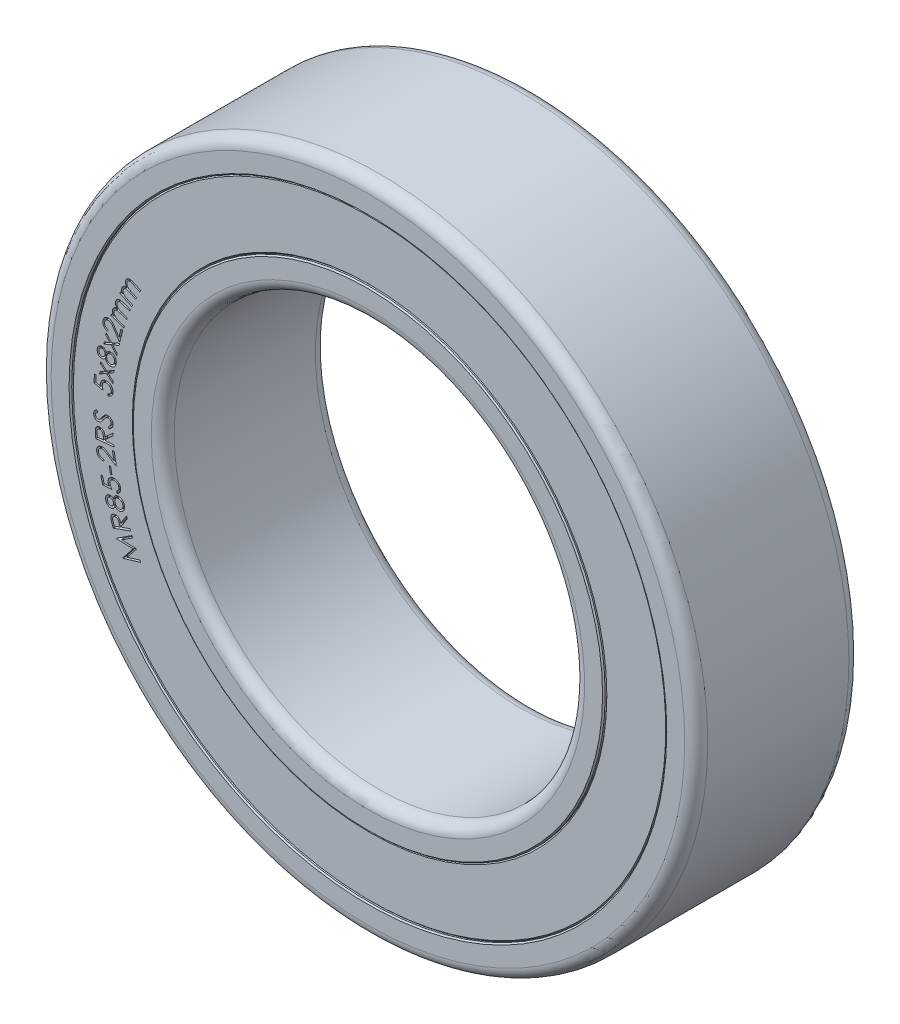
SolidWorks part; units mm, degrees
material "AISI 316 Annealed Stainless Steel Bar (SS)"
ref_plane "Front" through (0, 0, 0) normal (0, 0, 1) x (1, 0, 0)
ref_plane "Top" through (0, 0, 0) normal (0, 1, 0) x (1, 0, 0)
ref_plane "Right" through (0, 0, 0) normal (1, 0, 0) x (0, 0, -1)
sketch "LAYOUT R" plane through (0, 0, 0) normal (1, 0, 0) x (0, 0, -1)
  line L0 (-1, 2.5) -> (1, 2.5)
  line L1 (1, -4) -> (-1, -4) construction
  line L2 (1, -4) -> (1, 4) construction
  line L3 (1, 4) -> (-1, 4)
  line L4 (-1, -4) -> (-1, 4) construction
  line L5 (1, -4) -> (-1, 4) construction
  line L6 (1, 4) -> (-1, -4) construction
  line L7 (-1, 2.875) -> (1, 2.875)
  line L8 (-1, 3.625) -> (1, 3.625)
  line L11 (-17.5, 0) -> (17.5, 0) construction
  line L12 (-1, 4) -> (-1, 3.625)
  line L13 (1, 4) -> (1, 3.625)
  line L14 (-1, 3.625) -> (-1, 2.875)
  line L15 (1, 3.625) -> (1, 2.875)
  line L16 (-1, 2.875) -> (-1, 2.5)
  line L17 (1, 2.875) -> (1, 2.5)
  line L18 (-0.98, 3.625) -> (-0.98, 2.875)
  line L19 (0.98, 3.625) -> (0.98, 2.875)
  point P0 (0, 0)
  point P15 (0, 0)
  dimension "D1" = 2
  dimension "D2" = 8
  dimension "D3" = 2.5
  dimension "D6" = 0.02
  dimension "D7" = 0.02
  dimension "D4" = 2.875
  dimension "D5" = 3.625
sketch "Sketch R, INNER BODY" plane through (0, 0, 0) normal (1, 0, 0) x (0, 0, -1)
  line L0 (-1, 2.5) -> (1, 2.5) construction
  line L2 (-1, 2.875) -> (1, 2.875) construction
  line L4 (-1, 2.5) -> (1, 2.5)
  line L6 (-1, 2.875) -> (1, 2.875)
  line L8 (1, 2.875) -> (1, 2.5) construction
  line L9 (-1, 2.875) -> (-1, 2.5) construction
  line L10 (1, 2.875) -> (1, 2.5)
  line L11 (-1, 2.875) -> (-1, 2.5)
  line L12 (-17.5, 0) -> (17.5, 0) construction
  line L13 (-17.5, 0) -> (17.5, 0) construction
sketch "Sketch R, OUTER BODY" plane through (0, 0, 0) normal (1, 0, 0) x (0, 0, -1)
  line L2 (-1, 3.625) -> (1, 3.625) construction
  line L3 (1, 4) -> (-1, 4) construction
  line L6 (-1, 3.625) -> (1, 3.625)
  line L7 (1, 4) -> (-1, 4)
  line L8 (-17.5, 0) -> (17.5, 0) construction
  line L9 (-17.5, 0) -> (17.5, 0) construction
  line L10 (1, 4) -> (1, 3.625) construction
  line L11 (-1, 4) -> (-1, 3.625) construction
  line L12 (1, 4) -> (1, 3.625)
  line L13 (-1, 4) -> (-1, 3.625)
sketch "Sketch R, SEAL FACES" plane through (0, 0, 0) normal (1, 0, 0) x (0, 0, -1)
  line L0 (-17.5, 0) -> (17.5, 0) construction
  line L1 (-17.5, 0) -> (17.5, 0) construction
  line L3 (-1, 2.875) -> (1, 2.875) construction
  line L5 (-1, 3.625) -> (1, 3.625) construction
  line L7 (-0.98, 2.875) -> (0.98, 2.875)
  line L9 (-0.98, 3.625) -> (0.98, 3.625)
  line L10 (0.98, 3.625) -> (0.98, 2.875) construction
  line L11 (-0.98, 3.625) -> (-0.98, 2.875) construction
  line L12 (0.98, 3.625) -> (0.98, 2.875)
  line L13 (-0.98, 3.625) -> (-0.98, 2.875)
revolve "Revolve INNER BODY" add sketch "Sketch R, INNER BODY" angle 360 about L13
fillet "Fillet INNER BODY" radius 0.14 2 edges at (2.5, 0, 1) (2.5, 0, -1)
chamfer "Chamfer INNER BODY" distance 0.016 angle 45 2 edges at (2.875, 0, -1) (2.875, 0, 1)
revolve "Revolve OUTER BODY" add sketch "Sketch R, OUTER BODY" angle 360 about L9
fillet "Fillet OUTER BODY" radius 0.14 2 edges at (4, 0, -1) (4, 0, 1)
chamfer "Chamfer OUTER BODY" distance 0.016 angle 45 2 edges at (3.625, 0, 1) (3.625, 0, -1)
revolve "Revolve SEALS" add sketch "Sketch R, SEAL FACES" angle 360 about L1
chamfer "Chamfer SEALS" distance 0.016 angle 45 4 edges at (2.875, 0, -0.98) (3.625, 0, -0.98) (3.625, 0, 0.98) (2.875, 0, 0.98)
sketch "Sketch TEXT RADIUS 1 — MANUALLY ASSIGN TEXT AND FONT SIZE (FROM EQUATIONS)" plane through (0, 0, 0.98) normal (0, 0, 1) x (1, 0, 0)
  circle A0 centre (0, 0) radius 3.1375 construction
  text T0 "MR85-2RS  5x8x2mm" font "Century Gothic" height 0.225
  dimension "D1" = 6.275
extrude "Cut-Extrude SEAL LABEL 1" cut sketch "Sketch TEXT RADIUS 1 — MANUALLY ASSIGN TEXT AND FONT SIZE (FROM EQUATIONS)" against normal blind 0.05
sketch "Sketch TEXT RADIUS 2 — MANUALLY ASSIGN TEXT AND FONT SIZE (FROM EQUATIONS)" plane through (0, 0, -0.98) normal (0, 0, -1) x (-1, 0, 0)
  circle A0 centre (0, 0) radius 3.1375 construction
  text T0 "MR85-2RS  5x8x2mm" font "Century Gothic" height 0.225
  dimension "D1" = 6.275
extrude "Cut-Extrude SEAL LABEL 2" cut sketch "Sketch TEXT RADIUS 2 — MANUALLY ASSIGN TEXT AND FONT SIZE (FROM EQUATIONS)" against normal blind 0.05
equation "\"_i__BORE\"= 5"
equation "\"_i__OUTSIDE_DIAMETER\"= 8"
equation "\"_i__WIDTH\"= 2"
equation "\"_i_optional__TEXT_RADIUS_ADJUSTMENT\"= 0"
equation "\"_output__FONT_SIZE_mm\"= \"BODY_SPAN__SEAL__OF_RADIUS\" * \"param__FONT_SIZE_RATIO\"'MANUALLY ASSIGN TO FONT"
equation "\"BODY__HALF_WIDTH\"= \"_i__WIDTH\" / 2"
equation "\"BODY_SPAN___OF_DIAMETER\"= \"_i__OUTSIDE_DIAMETER\" - \"_i__BORE\""
equation "\"BODY_SPAN___OF_RADIUS\"= \"BODY_SPAN___OF_DIAMETER\" / 2"
equation "\"BODY_SPAN__BORE_AND_OD__OF RADIUS\"= ( \"BODY_SPAN___OF_RADIUS\" - \"BODY_SPAN__SEAL__OF_RADIUS\" ) / 2"
equation "\"BODY_SPAN__SEAL__OF_RADIUS\"= \"BODY_SPAN___OF_RADIUS\" * \"param__SEAL_PANEL_SPAN__RATIO_OF_BODY_RADIAN\""
equation "\"BORE__RADIUS\"= \"_i__BORE\" / 2"
equation "\"CORNER_RADII\"= \"_i__WIDTH\" * \"param__CORNER_RADII__ISO_MAX_RATIO_TO_WIDTH\""
equation "\"param__CORNER_RADII__ISO_MAX_RATIO_TO_WIDTH\"= 0.07'WHERE WIDTH IS LESS THAN DIAMETER"
equation "\"param__FONT_SIZE_RATIO\"= 0.3"
equation "\"param__SEAL_FACE_INSET__RATIO_OF_WIDTH\"= .01"
equation "\"param__SEAL_PANEL_SPAN__RATIO_OF_BODY_RADIAN\"= 0.5"
equation "\"param__SIDE_CHAMFERS__RATIO_TO_OD\"= 1 / 500"
equation "\"RING_INNER__OUTSIDE_RADIUS\"= \"BORE__RADIUS\" + \"BODY_SPAN__BORE_AND_OD__OF RADIUS\""
equation "\"RING_OUTER__OUTSIDE_RADIUS\"= ( \"_i__OUTSIDE_DIAMETER\" / 2 ) - \"BODY_SPAN__BORE_AND_OD__OF RADIUS\""
equation "\"SEAL_FACE_INSET\"= \"_i__WIDTH\" * \"param__SEAL_FACE_INSET__RATIO_OF_WIDTH\""
equation "\"SIDE_FACE_AND_SEAL_CHAMFERS\"= \"_i__OUTSIDE_DIAMETER\" * \"param__SIDE_CHAMFERS__RATIO_TO_OD\""
equation "\"TEXT_RADIUS\"= \"_i__BORE\" + ( \"BODY_SPAN___OF_DIAMETER\" / 2 ) - \"_output__FONT_SIZE_mm\" + \"_i_optional__TEXT_RADIUS_ADJUSTMENT\""
equation "\"D1@Chamfer INNER BODY\"=\"SIDE_FACE_AND_SEAL_CHAMFERS\""
equation "\"D1@Chamfer OUTER BODY\"=\"SIDE_FACE_AND_SEAL_CHAMFERS\""
equation "\"D1@Chamfer SEALS\"=\"SIDE_FACE_AND_SEAL_CHAMFERS\""
equation "\"D1@Fillet INNER BODY\"=\"CORNER_RADII\""
equation "\"D1@Fillet OUTER BODY\"=\"CORNER_RADII\""
equation "\"D1@LAYOUT R\"=\"_i__WIDTH\""
equation "\"D1@Sketch TEXT RADIUS 1 — MANUALLY ASSIGN TEXT AND FONT SIZE (FROM EQUATIONS)\" = \"TEXT_RADIUS\""
equation "\"D1@Sketch TEXT RADIUS 2 — MANUALLY ASSIGN TEXT AND FONT SIZE (FROM EQUATIONS)\" = \"TEXT_RADIUS\""
equation "\"D2@LAYOUT R\"=\"_i__OUTSIDE_DIAMETER\""
equation "\"D3@LAYOUT R\"=\"BORE__RADIUS\""
equation "\"D4@LAYOUT R\"=\"RING_INNER__OUTSIDE_RADIUS\""
equation "\"D5@LAYOUT R\"=\"RING_OUTER__OUTSIDE_RADIUS\""
